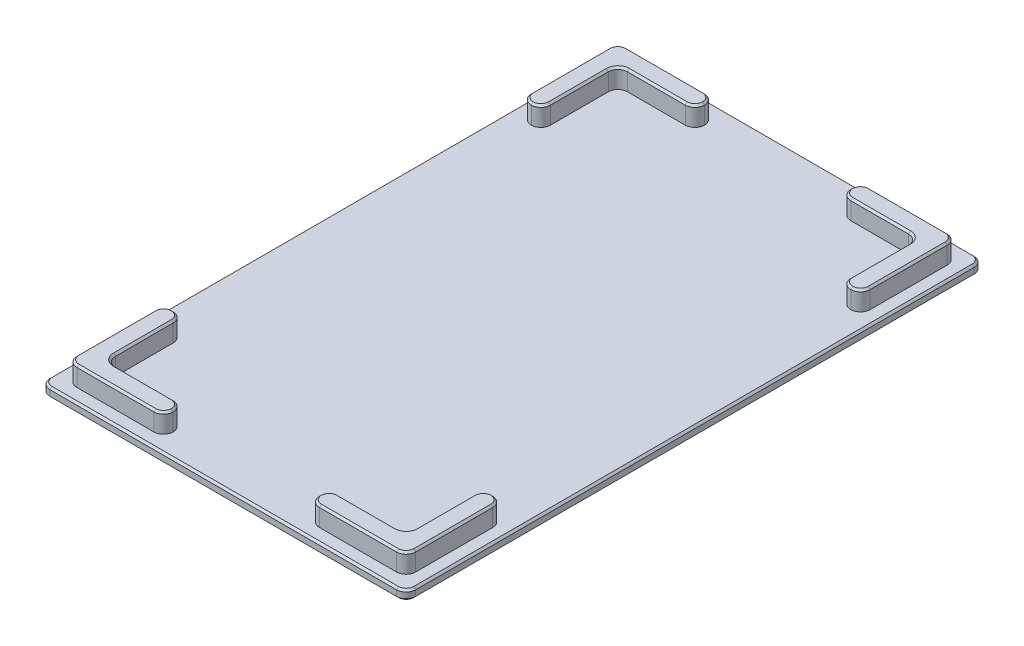
SolidWorks part; units mm, degrees
material "Nylon 101"
ref_plane "Front" through (0, 0, 0) normal (0, 0, 1) x (1, 0, 0)
ref_plane "Top" through (0, 0, 0) normal (0, 1, 0) x (1, 0, 0)
ref_plane "Right" through (0, 0, 0) normal (1, 0, 0) x (0, 0, -1)
sketch "Sketch1" plane through (0, 0, 0) normal (0, 1, 0) x (1, 0, 0)
  line L0 (45, 147.5) -> (-45, 147.5)
  line L1 (-45, 147.5) -> (-45, 2.5)
  line L2 (-45, 2.5) -> (45, 2.5)
  line L3 (45, 2.5) -> (45, 147.5)
  line L4 (-47.5, 0) -> (47.5, 0)
  line L5 (47.5, 0) -> (47.5, 150)
  line L6 (47.5, 150) -> (-47.5, 150)
  line L7 (-47.5, 150) -> (-47.5, 0)
extrude "Boss-Extrude1" add sketch "Sketch1" along normal blind 2.5 contours L2 L3 L0 L1 | L6 L7 L4 L5 L3 L2 L1 L0 region at (0, 0, -75) region at (-45.7245, 0, -75)
sketch "Sketch2" plane through (0, 2.5, 0) normal (0, 1, 0) x (1, 0, 0)
  line L0 (-44, 28.5) -> (-44, 3.5)
  line L1 (-44, 146.5) -> (-44, 3.5) construction
  line L2 (-39, 28.5) -> (-39, 8.5)
  line L3 (-39, 141.5) -> (-39, 8.5) construction
  line L4 (39, 141.5) -> (19, 141.5)
  line L5 (-39, 141.5) -> (-39, 121.5)
  line L6 (-39, 8.5) -> (-19, 8.5)
  line L7 (39, 8.5) -> (39, 28.5)
  line L8 (44, 146.5) -> (-44, 146.5)
  line L9 (-44, 146.5) -> (-44, 3.5)
  line L10 (-44, 3.5) -> (44, 3.5)
  line L11 (44, 3.5) -> (44, 146.5)
  line L12 (44, 146.5) -> (19, 146.5)
  line L13 (-44, 146.5) -> (-44, 121.5)
  line L14 (-44, 3.5) -> (-19, 3.5)
  line L15 (44, 3.5) -> (44, 28.5)
  line L16 (-47.5, 121.5) -> (-39, 121.5)
  line L17 (-47.5, 150) -> (-47.5, 0) construction
  line L18 (-44, 28.5) -> (-39, 28.5)
  line L19 (-19, 146.5) -> (-19, 141.5)
  line L20 (19, 3.5) -> (19, 8.5)
  line L21 (-19, 8.5) -> (-19, 3.5)
  line L22 (39, 121.5) -> (44, 121.5)
  line L23 (-19, 141.5) -> (-39, 141.5)
  line L24 (39, 141.5) -> (-39, 141.5) construction
  line L25 (-19, 146.5) -> (-44, 146.5)
  line L26 (44, 146.5) -> (-44, 146.5) construction
  line L27 (19, 141.5) -> (19, 146.5)
  line L28 (39, 121.5) -> (39, 141.5)
  line L29 (39, 8.5) -> (39, 141.5) construction
  line L30 (44, 121.5) -> (44, 146.5)
  line L31 (44, 3.5) -> (44, 146.5) construction
  line L32 (39, 28.5) -> (44, 28.5)
  line L33 (19, 8.5) -> (39, 8.5)
  line L34 (-39, 8.5) -> (39, 8.5) construction
  line L35 (19, 3.5) -> (44, 3.5)
  line L36 (-44, 3.5) -> (44, 3.5) construction
  dimension "D3" = 93
  dimension "D4" = 25
  dimension "D5" = 25
  dimension "D6" = 25
  dimension "D7" = 25
  dimension "D1" = 3.5
  dimension "D2" = 5
extrude "Boss-Extrude2" add sketch "Sketch2" along normal blind 5 contours L21 L6 L2 L18 L0 L14 | L20 L35 L15 L32 L7 L33 | L19 L25 L13 L16 L5 L23 | L22 L30 L12 L27 L4 L28 region at (-41.5, 2.5, -28.1464) region at (-43.6464, 2.5, -134) region at (19.3536, 2.5, -6) region at (31.5, 2.5, -146.1464)
fillet "Fillet1" radius 2.5 28 edges at (47.5, 1.25, -150) (47.5, 1.25, 0) (-47.5, 1.25, 0) (-47.5, 1.25, -150) (44, 5, -146.5) (19, 5, -146.5) (19, 5, -141.5) (39, 5, -141.5) (39, 5, -121.5) (44, 5, -121.5) (-19, 5, -8.5) (-39, 5, -8.5) (-39, 5, -28.5) (-44, 5, -28.5) (-44, 5, -3.5) (-19, 5, -3.5) (-19, 5, -146.5) (-44, 5, -121.5) (-39, 5, -121.5) (-39, 5, -141.5) (-19, 5, -141.5) (19, 5, -3.5) (44, 5, -3.5) (44, 5, -28.5) (39, 5, -28.5) (39, 5, -8.5) (19, 5, -8.5) (-44, 5, -146.5)
chamfer "Chamfer1" distance 0.5 angle 45 56 edges at (-38.2678, 7.5, -9.2322) (-29, 7.5, -8.5) (-19.7322, 7.5, -7.7678) (-19.7322, 7.5, -4.2322) (-31.5, 7.5, -3.5) (-43.2678, 7.5, -4.2322) (-44, 7.5, -16) (-43.2678, 7.5, -27.7678) (-39.7322, 7.5, -27.7678) (-39, 7.5, -18.5) (19.7322, 7.5, -4.2322) (19.7322, 7.5, -7.7678) (29, 7.5, -8.5) (38.2678, 7.5, -9.2322) (39, 7.5, -18.5) (39.7322, 7.5, -27.7678) (43.2678, 7.5, -27.7678) (44, 7.5, -16) (43.2678, 7.5, -4.2322) (31.5, 7.5, -3.5) (43.2678, 7.5, -122.2322) (39.7322, 7.5, -122.2322) (39, 7.5, -131.5) (38.2678, 7.5, -140.7678) (29, 7.5, -141.5) (19.7322, 7.5, -142.2322) (19.7322, 7.5, -145.7678) (31.5, 7.5, -146.5) (43.2678, 7.5, -145.7678) (44, 7.5, -134) (-43.2678, 7.5, -145.7678) (-31.5, 7.5, -146.5) (-19.7322, 7.5, -145.7678) (-19.7322, 7.5, -142.2322) (-29, 7.5, -141.5) (-38.2678, 7.5, -140.7678) (-39, 7.5, -131.5) (-39.7322, 7.5, -122.2322) (-43.2678, 7.5, -122.2322) (-44, 7.5, -134) (0, 0, 0) (46.7678, 0, -0.7322) (-46.7678, 0, -0.7322) (47.5, 0, -75) (-47.5, 0, -75) (46.7678, 0, -149.2678) (-46.7678, 0, -149.2678) (0, 0, -150) (0, 2.5, 0) (46.7678, 2.5, -0.7322) (-46.7678, 2.5, -0.7322) (47.5, 2.5, -75) (-47.5, 2.5, -75) (46.7678, 2.5, -149.2678) (-46.7678, 2.5, -149.2678) (0, 2.5, -150)
